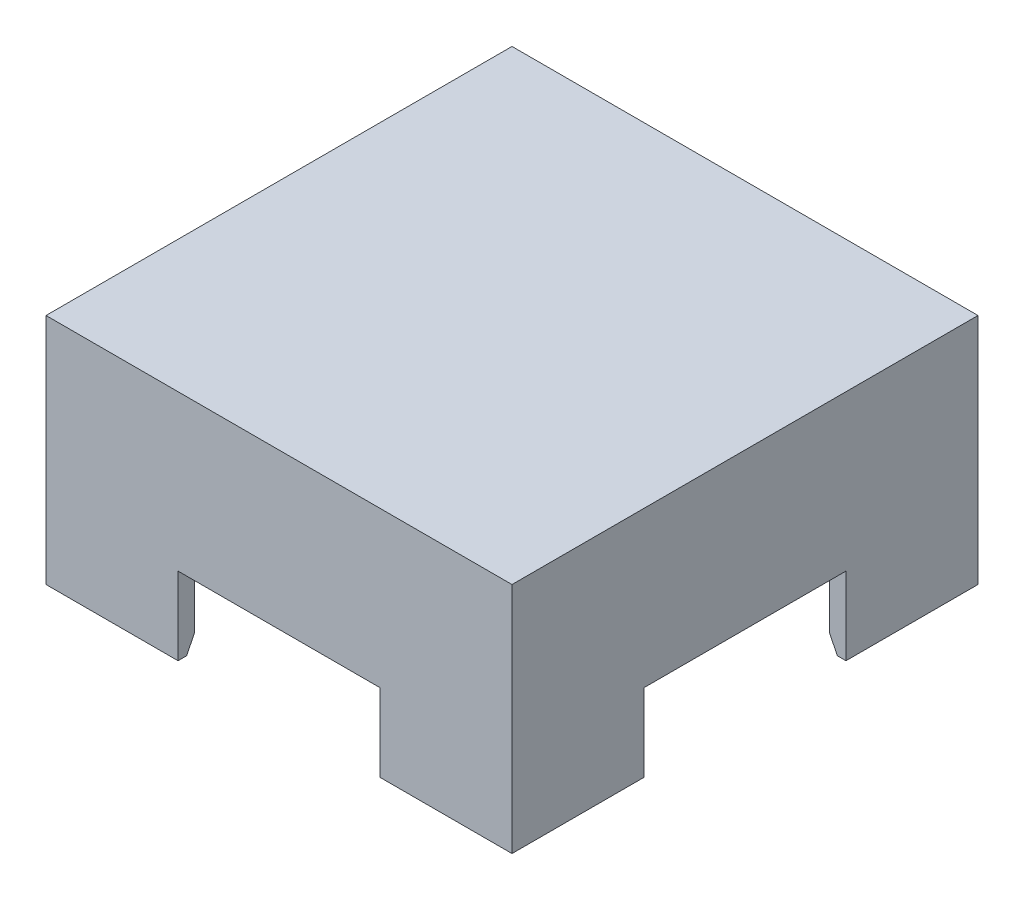
SolidWorks part; units mm, degrees
ref_plane "Front Plane" through (0, 0, 0) normal (0, 0, 1) x (1, 0, 0)
ref_plane "Top Plane" through (0, 0, 0) normal (0, 1, 0) x (1, 0, 0)
ref_plane "Right Plane" through (0, 0, 0) normal (1, 0, 0) x (0, 0, -1)
sketch "Sketch1" plane through (0, 1478.6171, 0) normal (0, 1, 0) x (1, 0, 0)
  line L1 (-530.1492, -768.8296) -> (-453.9492, -768.8296)
  line L2 (-530.1492, -768.8296) -> (-530.1492, -845.0296)
  line L3 (-530.1492, -845.0296) -> (-453.9492, -845.0296)
  line L4 (-453.9492, -768.8296) -> (-453.9492, -845.0296)
  line L5 (-530.1492, -768.8296) -> (-453.9492, -845.0296) construction
  line L6 (-530.1492, -845.0296) -> (-453.9492, -768.8296) construction
  point P0 (-492.0492, -806.9296)
  dimension "D1" = 76.2
  dimension "D2" = 76.2
extrude "Boss-Extrude1" add sketch "Sketch1" along normal blind 25.4
sketch "Sketch2" plane through (0, 1478.6171, 0) normal (0, -1, 0) x (-1, 0, 0)
  line L1 (463.4742, -778.3546) -> (520.6242, -778.3546)
  line L2 (463.4742, -778.3546) -> (463.4742, -835.5046)
  line L3 (463.4742, -835.5046) -> (520.6242, -835.5046)
  line L4 (520.6242, -778.3546) -> (520.6242, -835.5046)
  line L5 (463.4742, -778.3546) -> (520.6242, -835.5046) construction
  line L6 (463.4742, -835.5046) -> (520.6242, -778.3546) construction
  point P0 (492.0492, -806.9296)
  dimension "D1" = 57.15
  dimension "D2" = 57.15
extrude "Cut-Extrude1" cut sketch "Sketch2" against normal blind 19.05
sketch "Sketch3" plane through (0, 1478.6171, 0) normal (0, -1, 0) x (-1, 0, 0)
  line L0 (530.1492, -768.8296) -> (530.1492, -845.0296) construction
  line L1 (530.1492, -790.4196) -> (527.4822, -790.4196)
  line L3 (530.1492, -823.4396) -> (527.4822, -823.4396)
  line L5 (453.9492, -768.8296) -> (530.1492, -768.8296) construction
  line L7 (508.5592, -768.8296) -> (508.5592, -771.4966)
  line L9 (475.5392, -768.8296) -> (475.5392, -771.4966)
  line L10 (530.1492, -845.0296) -> (453.9492, -845.0296) construction
  line L12 (508.5592, -845.0296) -> (508.5592, -842.3626)
  line L14 (475.5392, -845.0296) -> (475.5392, -842.3626)
  line L15 (453.9492, -845.0296) -> (453.9492, -768.8296) construction
  line L16 (453.9492, -823.4396) -> (456.6162, -823.4396)
  line L18 (453.9492, -790.4196) -> (456.6162, -790.4196)
  line L24 (530.1492, -790.4196) -> (530.1492, -768.8296)
  line L25 (530.1492, -768.8296) -> (508.5592, -768.8296)
  line L26 (508.5592, -771.4966) -> (527.4822, -771.4966)
  line L27 (527.4822, -771.4966) -> (527.4822, -790.4196)
  line L28 (530.1492, -823.4396) -> (530.1492, -845.0296)
  line L29 (530.1492, -845.0296) -> (508.5592, -845.0296)
  line L30 (508.5592, -842.3626) -> (527.4822, -842.3626)
  line L31 (527.4822, -842.3626) -> (527.4822, -823.4396)
  line L32 (475.5392, -845.0296) -> (453.9492, -845.0296)
  line L33 (453.9492, -845.0296) -> (453.9492, -823.4396)
  line L34 (475.5392, -842.3626) -> (456.6162, -842.3626)
  line L35 (456.6162, -842.3626) -> (456.6162, -823.4396)
  line L36 (453.9492, -790.4196) -> (453.9492, -768.8296)
  line L37 (453.9492, -768.8296) -> (475.5392, -768.8296)
  line L38 (475.5392, -771.4966) -> (456.6162, -771.4966)
  line L39 (456.6162, -771.4966) -> (456.6162, -790.4196)
  dimension "D1" = 21.59
  dimension "D2" = 21.59
  dimension "D3" = 21.59
  dimension "D4" = 21.59
  dimension "D5" = 21.59
  dimension "D6" = 21.59
  dimension "D7" = 21.59
  dimension "D8" = 21.59
extrude "Boss-Extrude2" add sketch "Sketch3" along normal blind 12.7
chamfer "Chamfer1" distance 2.54 distance2 1.27 8 edges at (-527.4822, 1465.9171, 780.9581) (-518.0207, 1465.9171, 771.4966) (-466.0777, 1465.9171, 771.4966) (-456.6162, 1465.9171, 780.9581) (-456.6162, 1465.9171, 832.9011) (-466.0777, 1465.9171, 842.3626) (-527.4822, 1465.9171, 832.9011) (-518.0207, 1465.9171, 842.3626) first distance on face at (-527.4822, 1472.2671, 780.9581) first distance on face at (-518.0207, 1472.2671, 771.4966) first distance on face at (-466.0777, 1472.2671, 771.4966) first distance on face at (-456.6162, 1472.2671, 780.9581) first distance on face at (-456.6162, 1472.2671, 832.9011) first distance on face at (-466.0777, 1472.2671, 842.3626) first distance on face at (-527.4822, 1472.2671, 832.9011) first distance on face at (-518.0207, 1472.2671, 842.3626)
